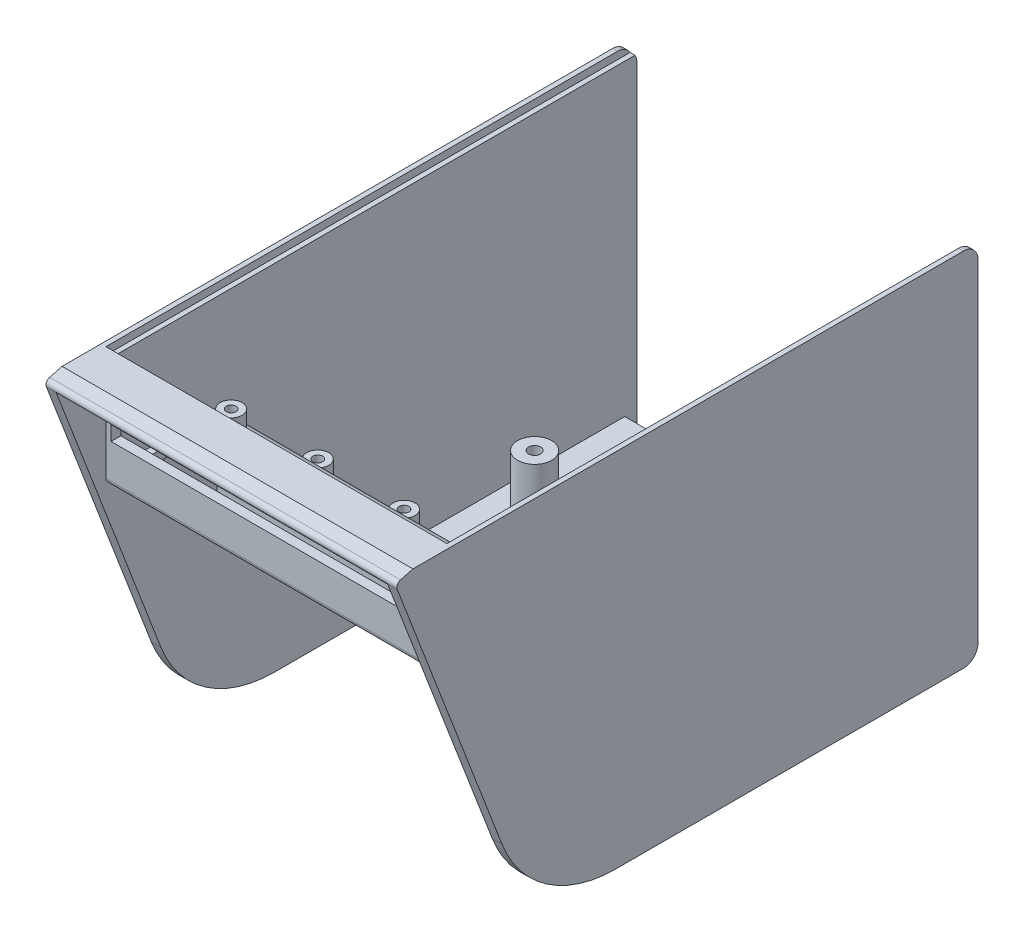
SolidWorks part; units mm, degrees
ref_plane "Front Plane" through (0, 0, 0) normal (0, 0, 1) x (1, 0, 0)
ref_plane "Top Plane" through (0, 0, 0) normal (0, 1, 0) x (1, 0, 0)
ref_plane "Right Plane" through (0, 0, 0) normal (1, 0, 0) x (0, 0, -1)
sketch "Sketch1" plane through (0, 0, 0) normal (0, 1, 0) x (1, 0, 0)
  line L1 (-36, -54.49) -> (36, -54.49)
  line L2 (-36, -54.49) -> (-36, 54.49)
  line L3 (-36, 54.49) -> (36, 54.49)
  line L4 (36, -54.49) -> (36, 54.49)
  line L5 (-36, -54.49) -> (36, 54.49) construction
  line L6 (-36, 54.49) -> (36, -54.49) construction
  point P0 (0, 0)
  dimension "D1" = 72
  dimension "D2" = 108.98
extrude "Boss-Extrude1" add sketch "Sketch1" along normal blind 66.66
sketch "Sketch2" plane through (36, 0, 0) normal (1, 0, 0) x (0, 0, -1)
  line L0 (-54.49, 66.66) -> (-54.49, 43.24)
  line L1 (-54.49, 66.66) -> (-54.49, 0) construction
  line L2 (-54.49, 43.24) -> (-31.71, 43.24)
  line L3 (-31.71, 43.24) -> (-31.71, 25.46)
  line L4 (-31.71, 25.46) -> (-14.01, 25.46)
  line L5 (-14.01, 25.46) -> (-14.01, 7.68)
  line L6 (-14.01, 7.68) -> (3.85, 7.68)
  line L7 (3.85, 7.68) -> (3.85, 0)
  line L8 (-54.49, 0) -> (54.49, 0) construction
  line L9 (54.49, 66.66) -> (54.49, 0) construction
  line L10 (-54.49, 66.66) -> (54.49, 66.66) construction
  dimension "D1" = 23.42
  dimension "D2" = 86.2
  dimension "D3" = 41.2
  dimension "D4" = 58.98
  dimension "D5" = 68.5
  dimension "D6" = 50.64
extrude "Cut-Extrude1" cut sketch "Sketch2" against normal through all and the other way through all flip side to cut
fillet "Fillet1" radius 1 7 edges at (0, 7.68, -3.85) (0, 25.46, 14.01) (0, 43.24, 31.71) (0, 43.24, 54.49) (0, 25.46, 31.71) (0, 7.68, 14.01) (0, 0, -3.85)
shell "Shell1" thickness 2
sketch "Sketch3" plane through (0, 43.24, 0) normal (0, -1, 0) x (1, 0, 0)
  line L0 (-36, 54.49) -> (36, 54.49) construction
  line L1 (-32.5, 47.39) -> (32.5, 47.39)
  line L2 (-32.5, 47.39) -> (-32.5, 37.39)
  line L3 (-32.5, 37.39) -> (32.5, 37.39)
  line L4 (32.5, 47.39) -> (32.5, 37.39)
  line L5 (0, 0) -> (0, 59.3951) construction
  dimension "D1" = 65
  dimension "D2" = 10
  dimension "D3" = 7.1
extrude "Cut-Extrude2" cut sketch "Sketch3" against normal up to next
sketch "Sketch4" plane through (0, 25.46, 0) normal (0, -1, 0) x (1, 0, 0)
  line L0 (-32.5, 47.39) -> (-32.5, 37.39) construction
  line L1 (-32.5, 29.61) -> (32.5, 29.61)
  line L2 (-32.5, 29.61) -> (-32.5, 19.61)
  line L3 (-32.5, 19.61) -> (32.5, 19.61)
  line L4 (32.5, 29.61) -> (32.5, 19.61)
  line L5 (32.5, 37.39) -> (32.5, 47.39) construction
  line L6 (36, 31.71) -> (-36, 31.71) construction
  dimension "D1" = 2.1
  dimension "D2" = 10
extrude "Cut-Extrude3" cut sketch "Sketch4" against normal up to next
sketch "Sketch5" plane through (0, 7.68, 0) normal (0, -1, 0) x (1, 0, 0)
  line L0 (-32.5, 29.61) -> (-32.5, 19.61) construction
  line L1 (-32.5, 11.91) -> (32.5, 11.91)
  line L2 (-32.5, 11.91) -> (-32.5, 1.91)
  line L3 (-32.5, 1.91) -> (32.5, 1.91)
  line L4 (32.5, 11.91) -> (32.5, 1.91)
  line L5 (32.5, 19.61) -> (32.5, 29.61) construction
  line L6 (36, 14.01) -> (-36, 14.01) construction
  dimension "D1" = 10
  dimension "D2" = 2.1
extrude "Cut-Extrude4" cut sketch "Sketch5" against normal up to next
sketch "Sketch7" plane through (0, 45.24, 0) normal (0, 1, 0) x (1, 0, 0)
  line L0 (-32.5, -37.39) -> (32.5, -37.39) construction
  circle A0 centre (-28, -34.79) radius 2.25
  circle A1 centre (28, -34.79) radius 2.25
  dimension "D1" = 4.5
  dimension "D4" = 28
  dimension "D5" = 4.5
  dimension "D2" = 28
  dimension "D3" = 2.6
extrude "Boss-Extrude2" add sketch "Sketch7" along normal blind 4.5 and the other way up to next (2 mm away)
sketch "Sketch8" plane through (0, 27.46, 0) normal (0, 1, 0) x (1, 0, 0)
  line L0 (-32.5, -19.61) -> (32.5, -19.61) construction
  circle A0 centre (-28, -17.01) radius 2.25
  circle A1 centre (28, -17.01) radius 2.25
  dimension "D1" = 28
  dimension "D4" = 4.5
  dimension "D2" = 28
  dimension "D3" = 2.6
extrude "Boss-Extrude3" add sketch "Sketch8" along normal blind 4.5 and the other way up to next
sketch "Sketch9" plane through (0, 9.68, 0) normal (0, 1, 0) x (1, 0, 0)
  line L0 (-32.5, -1.91) -> (32.5, -1.91) construction
  circle A0 centre (-28, 0.69) radius 2.25
  circle A1 centre (28, 0.69) radius 2.25
  dimension "D1" = 4.5
  dimension "D3" = 28
  dimension "D5" = 4.5
  dimension "D2" = 2.6
  dimension "D4" = 28
extrude "Boss-Extrude4" add sketch "Sketch9" along normal blind 4.5 and the other way up to next (2 mm away)
sketch "Sketch10" plane through (0, 0, 54.49) normal (0, 0, 1) x (1, 0, 0)
  line L1 (-32.936, 54.3583) -> (33.0803, 54.3583)
  line L2 (-32.936, 54.3583) -> (-32.936, 51.34)
  line L3 (-32.936, 51.34) -> (33.0803, 51.34)
  line L4 (33.0803, 54.3583) -> (33.0803, 51.34)
extrude "Cut-Extrude5" cut sketch "Sketch10" against normal up to next
sketch "Sketch11" plane through (0, 2, 0) normal (0, 1, 0) x (1, 0, 0)
  line L0 (34, 54.49) -> (-34, 54.49) construction
  line L1 (-36, 54.49) -> (-36, -54.49) construction
  line L2 (36, -54.49) -> (36, 54.49) construction
  circle A0 centre (-25, 24.49) radius 3.5
  circle A1 centre (25, 24.49) radius 3.5
  dimension "D1" = 7
  dimension "D2" = 7
  dimension "D3" = 30
  dimension "D4" = 50
  dimension "D6" = 11
  dimension "D5" = 11
extrude "Boss-Extrude5" add sketch "Sketch11" along normal blind 12.22
sketch "Sketch12" plane through (-36, 0, 0) normal (-1, 0, 0) x (0, 0, 1)
  line L0 (54.49, 66.66) -> (65.49, 66.66)
  line L1 (-54.49, 0) -> (-4.85, 0) construction
  line L2 (65.49, 66.66) -> (43.1801, 8.5408)
  line L3 (-54.49, -7.5) -> (-54.49, 0)
  line L4 (-54.49, -7.5) -> (19.8406, -7.5)
  line L5 (-54.49, 0) -> (54.49, 66.66)
  arc A1 (43.1801, 8.5408) -> (19.8406, -7.5) centre (19.8406, 17.5) cw
  dimension "D4" = 25
  dimension "D1" = 11
  dimension "D3" = 7.5
  dimension "D5" = 69
extrude "Boss-Extrude6" add sketch "Sketch12" against normal blind 2
mirror "Mirror1" about plane through (0, 0, 0) normal (1, 0, 0) of "Boss-Extrude6"
sketch "Sketch20" plane through (0, 66.66, 0) normal (0, 1, 0) x (1, 0, 0)
  line L1 (-34, -65.49) -> (34, -65.49)
  line L2 (-34, -65.49) -> (-34, -54.49)
  line L3 (-34, -54.49) -> (34, -54.49)
  line L4 (34, -65.49) -> (34, -54.49)
extrude "Boss-Extrude7" add sketch "Sketch20" against normal blind 2
sketch "Sketch21" plane through (36, 0, 0) normal (1, 0, 0) x (0, 0, -1)
  line L0 (-65.49, 66.66) -> (-64.3761, 63.7583)
  line L1 (-43.1801, 8.5408) -> (-65.49, 66.66) construction
  line L2 (-64.3761, 63.7583) -> (-66.4372, 63.7583)
  line L3 (-66.4372, 63.7583) -> (-65.49, 66.66)
extrude "Cut-Extrude12" cut sketch "Sketch21" against normal through all
chamfer "Chamfer1" distance 4 angle 15 1 edges at (0, 66.66, 65.49)
fillet "Fillet3" radius 1 1 edges at (0, 65.6882, 65.1169)
sketch "Sketch13" plane through (0, 0, 0) normal (0, -1, 0) x (1, 0, 0)
  line L1 (-34, -54.49) -> (34.195, -54.49)
  line L2 (-34, -54.49) -> (-34, -51.99)
  line L3 (-34, -51.99) -> (34.195, -51.99)
  line L4 (34.195, -54.49) -> (34.195, -51.99)
  dimension "D1" = 2.5
extrude "Cut-Extrude6" cut sketch "Sketch13" against normal up to next
fillet "Fillet4" radius 3 2 edges at (-35, 66.66, -54.49) (35.0975, 66.66, -54.49)
fillet "Fillet5" radius 3 2 edges at (-35, -7.5, -54.49) (35, -7.5, -54.49)
sketch "Sketch14" plane through (0, 66.66, 0) normal (0, 1, 0) x (1, 0, 0)
  line L8 (-35, 60.2303) -> (35, 60.2303)
  line L9 (35, -53.49) -> (35, -32.71)
  line L10 (-35, -53.49) -> (35, -53.49)
  line L11 (-35, 51.49) -> (-35, -53.49)
  line L13 (-35, -53.49) -> (35, -53.49)
  line L14 (-35, 60.2303) -> (-35, -53.49)
  line L15 (35, -53.49) -> (35, 60.2303)
  dimension "D1" = 1
extrude "Cut-Extrude7" cut sketch "Sketch14" against normal blind 1.5
sketch "Sketch16" plane through (0, 0, 0) normal (0, -1, 0) x (1, 0, 0)
  line L0 (34, -51.99) -> (-34, -51.99) construction
  line L1 (-34, -51.49) -> (-34, 19.8406) construction
  line L3 (34, -4.85) -> (34, -51.99) construction
  circle A0 centre (-25, -24.49) radius 1.25
  circle A1 centre (25, -24.49) radius 1.25
  dimension "D1" = 2.5
  dimension "D2" = 2.5
  dimension "D3" = 27.5
  dimension "D4" = 27.5
  dimension "D5" = 9
  dimension "D6" = 9
extrude "Cut-Extrude8" cut sketch "Sketch16" against normal up to next
sketch "Sketch17" plane through (0, 14.18, 0) normal (0, 1, 0) x (1, 0, 0)
  circle A0 centre (-28, 0.69) radius 1
  circle A1 centre (28, 0.69) radius 1
  dimension "D1" = 2
  dimension "D2" = 2
extrude "Cut-Extrude9" cut sketch "Sketch17" against normal blind 4
sketch "Sketch18" plane through (0, 31.96, 0) normal (0, 1, 0) x (1, 0, 0)
  circle A0 centre (-28, -17.01) radius 1
  circle A1 centre (28, -17.01) radius 1
  dimension "D1" = 2
  dimension "D2" = 2
extrude "Cut-Extrude10" cut sketch "Sketch18" against normal blind 4
sketch "Sketch19" plane through (0, 49.74, 0) normal (0, 1, 0) x (1, 0, 0)
  circle A0 centre (-28, -34.79) radius 1
  circle A1 centre (28, -34.79) radius 1
  dimension "D1" = 2
  dimension "D2" = 2
extrude "Cut-Extrude11" cut sketch "Sketch19" against normal blind 4
